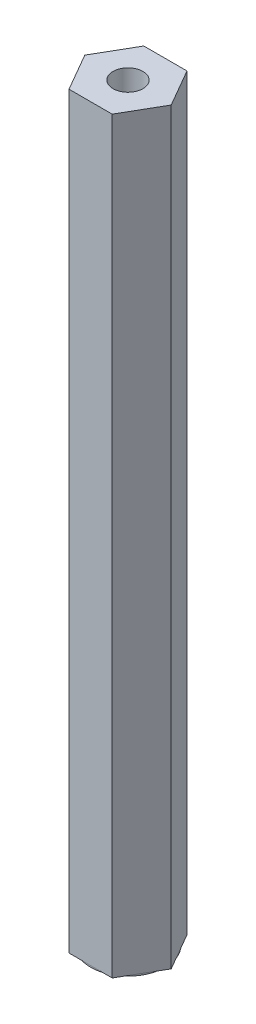
SolidWorks part; units mm, degrees
ref_plane "Front" through (0, 0, 0) normal (0, 0, 1) x (1, 0, 0)
ref_plane "Top" through (0, 0, 0) normal (0, 1, 0) x (1, 0, 0)
ref_plane "Right" through (0, 0, 0) normal (1, 0, 0) x (0, 0, -1)
sketch "Sketch1" plane through (0, 0, 0) normal (0, 1, 0) x (1, 0, 0)
  line L1 (7.3323, 0) -> (3.6662, 6.35)
  line L2 (3.6662, 6.35) -> (-3.6662, 6.35)
  line L3 (-3.6662, 6.35) -> (-7.3323, 0)
  line L4 (-7.3323, 0) -> (-3.6662, -6.35)
  line L5 (-3.6662, -6.35) -> (3.6662, -6.35)
  line L6 (3.6662, -6.35) -> (7.3323, 0)
  circle A0 centre (0, 0) radius 6.35 construction
extrude "Boss-Extrude1" add sketch "Sketch1" along normal blind 127
sketch "Sketch2" plane through (0, 127, 0) normal (0, 1, 0) x (1, 0, 0)
  circle A0 centre (0, 0) radius 2.54
  dimension "D1" = 5.08
extrude "Cut-Extrude1" cut sketch "Sketch2" against normal blind 25.4
sketch "Sketch3" plane through (0, 0, 0) normal (0, -1, 0) x (1, 0, 0)
  circle A0 centre (0, 0) radius 6.35
extrude "Boss-Extrude2" add sketch "Sketch3" along normal blind 0.254
